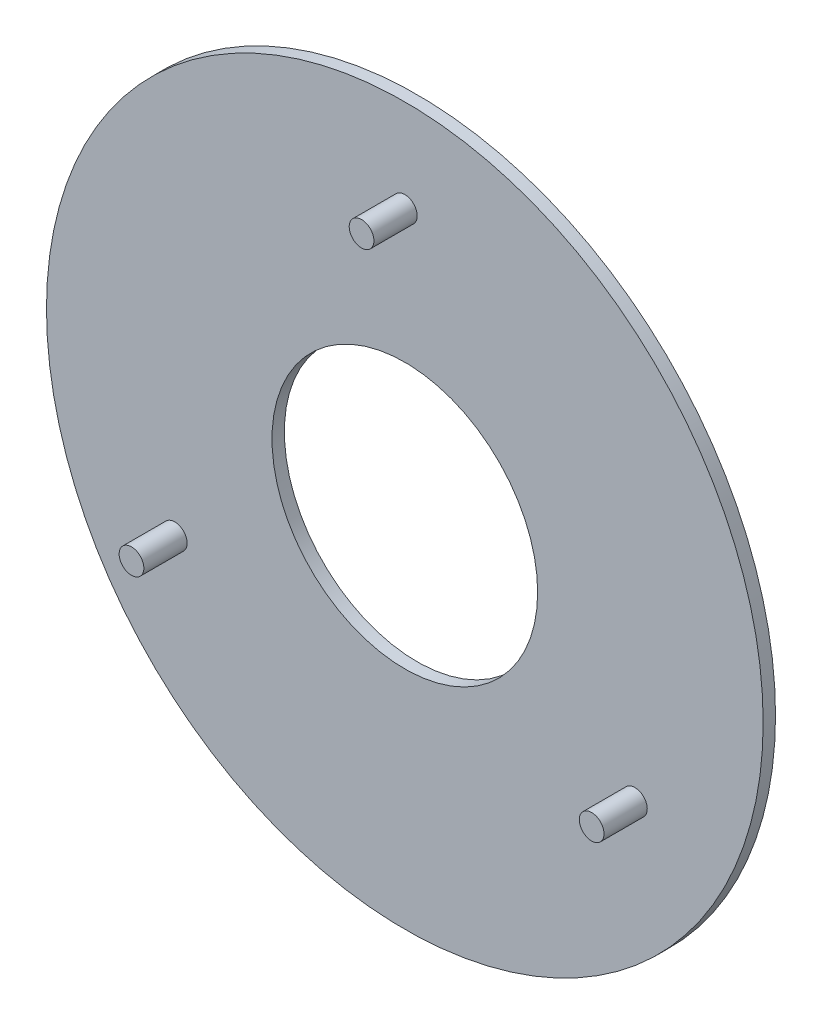
SolidWorks part; units mm, degrees
material "AISI 316 Stainless Steel Sheet (SS)"
ref_plane "Front Plane" through (0, 0, 0) normal (0, 0, 1) x (1, 0, 0)
ref_plane "Top Plane" through (0, 0, 0) normal (0, 1, 0) x (1, 0, 0)
ref_plane "Right Plane" through (0, 0, 0) normal (1, 0, 0) x (0, 0, -1)
sketch "Sketch1" plane through (0, 0, 0) normal (0, 0, 1) x (1, 0, 0)
  circle A0 centre (0, 0) radius 21.5
  circle A1 centre (0, 0) radius 58
  circle A2 centre (0, 0) radius 55 construction
  circle A3 centre (0, 0) radius 23.5 construction
  dimension "D1" = 43
  dimension "D2" = 116
  dimension "D3" = 2
  dimension "D4" = 3
extrude "Boss-Extrude1" add sketch "Sketch1" against normal blind 2 contours A1
sketch "Sketch2" plane through (0, 0, 0) normal (0, 0, 1) x (1, 0, 0)
  circle A0 centre (0, 43) radius 2
  dimension "D1" = 4
  dimension "D2" = 43
extrude "Boss-Extrude2" add sketch "Sketch2" along normal blind 7
sketch "Sketch4" plane through (0, 0, 0) normal (1, 0, 0) x (0, 0, -1)
  line L0 (0, 0) -> (50000, 0) construction
pattern_circular "CirPattern1" count 3 over 360 about axis through (0, 0, 0) along (0, 0, -1) of "Boss-Extrude2"
extrude "Cut-Extrude1" cut sketch "Sketch1<3>" against normal through all contours A0 region at (0, 0, 0)
sketch "Sketch1<3>" plane through (0, 0, 0) normal (0, 0, 1) x (1, 0, 0) same geometry as "Sketch1"
